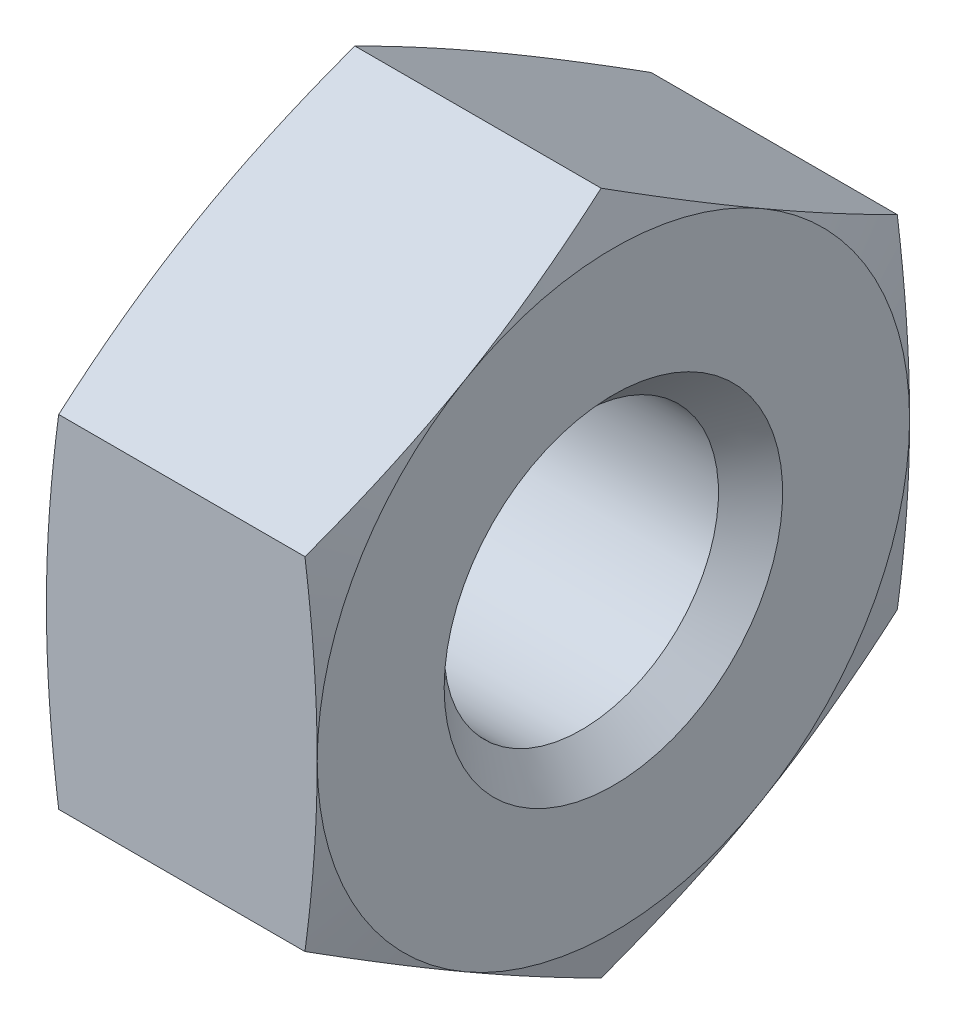
SolidWorks part; units mm, degrees
material "市購件"
ref_plane "前基準面" through (0, 0, 0) normal (0, 0, 1) x (1, 0, 0)
ref_plane "上基準面" through (0, 0, 0) normal (0, 1, 0) x (1, 0, 0)
ref_plane "右基準面" through (0, 0, 0) normal (1, 0, 0) x (0, 0, -1)
sketch "草圖1" plane through (0, 0, 0) normal (0, 0, 1) x (1, 0, 0)
  line L0 (-1.6, 0) -> (-1.6, 3.5)
  line L1 (-1.6, 3.5) -> (-1.4124, 4.2)
  line L2 (-1.4124, 4.2) -> (1.4124, 4.2)
  line L3 (1.4124, 4.2) -> (1.6, 3.5)
  line L4 (1.6, 3.5) -> (1.6, 0)
  line L5 (1.6, 0) -> (-1.6, 0)
  line L6 (1.6, 0) -> (-1.6, 0) construction
revolve "旋轉1" add sketch "草圖1" angle 360 about L6 reverse direction yes
sketch "草圖2" plane through (0, 0, 0) normal (0, 0, 1) x (1, 0, 0)
  line L0 (-1.6, 0) -> (-1.6, 2)
  line L1 (-1.6, 2) -> (-1.221, 1.621)
  line L2 (-1.221, 1.621) -> (1.221, 1.621)
  line L3 (1.221, 1.621) -> (1.6, 2)
  line L4 (1.6, 2) -> (1.6, 0)
  line L5 (1.6, 0) -> (-1.6, 0)
  line L6 (1.6, 0) -> (-1.6, 0) construction
revolve "除料-旋轉1" cut sketch "草圖2" angle 360 about L6 reverse direction yes
cosmetic thread "裝飾螺紋線1" parameters "D1"=3.2, "D2"=4
sketch "草圖3" plane through (0, 0, 0) normal (1, 0, 0) x (0, 0, -1)
  line L0 (-7, -7) -> (7, -7)
  line L1 (7, -7) -> (7, 7)
  line L2 (7, 7) -> (-7, 7)
  line L3 (-7, 7) -> (-7, -7)
  line L4 (-3.5, 2.0207) -> (-3.5, -2.0207)
  line L5 (-3.5, -2.0207) -> (0, -4.0415)
  line L6 (0, -4.0415) -> (3.5, -2.0207)
  line L7 (3.5, -2.0207) -> (3.5, 2.0207)
  line L8 (3.5, 2.0207) -> (0, 4.0415)
  line L9 (0, 4.0415) -> (-3.5, 2.0207)
extrude "除料-伸長1" cut sketch "草圖3" along normal blind 3.2 and the other way blind 3.2
ref_plane "平面1" through (1.6, 0, 0) normal (1, 0, 0) x (0, 0, -1)
ref_plane "nut_to_pin XY" through (1.6, 0, 0) normal (1, 0, 0) x (0, 0, -1)
ref_plane "nut_to_pin XZ" through (0, 0, 0) normal (0, -1, 0) x (-1, 0, 0)
ref_plane "nut_to_pin YZ" through (0, 0, 0) normal (0, 0, -1) x (-1, 0, 0)
ref_axis "nut_to_pin X" through (1.6, 0, 80.9) along (0, 0, -1)
ref_axis "nut_to_pin Y" through (1.6, -50, 0) along (0, 1, 0)
ref_axis "nut_to_pin Z" through (80.9, 0, 0) along (-1, 0, 0)
sketch3d "nut_to_pin"
  point P0 (1.6, 0, 0)
